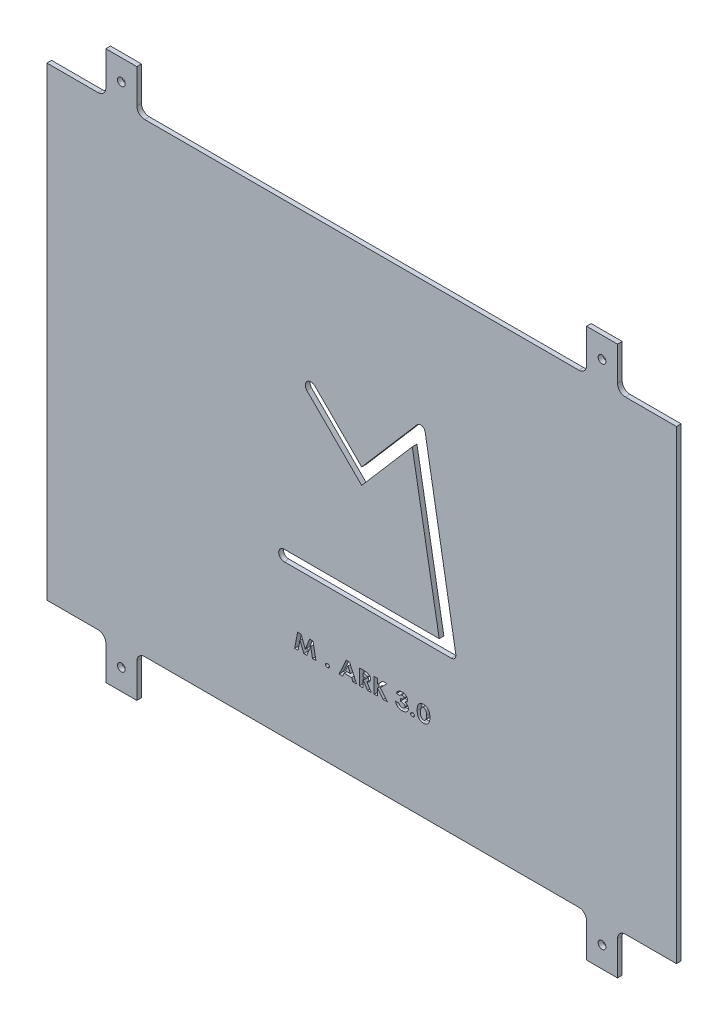
SolidWorks part; units mm, degrees
ref_plane "Front Plane" through (0, 0, 0) normal (0, 0, 1) x (1, 0, 0)
ref_plane "Top Plane" through (0, 0, 0) normal (0, 1, 0) x (1, 0, 0)
ref_plane "Right Plane" through (0, 0, 0) normal (1, 0, 0) x (0, 0, -1)
sketch "Sketch1" plane through (0, 0, 0) normal (0, 0, 1) x (1, 0, 0)
  line L1 (-203, -150) -> (203, -150)
  line L2 (-203, -150) -> (-203, 150)
  line L3 (-203, 150) -> (203, 150)
  line L4 (203, -150) -> (203, 150)
  line L5 (-203, -150) -> (203, 150) construction
  line L6 (-203, 150) -> (203, -150) construction
  point P0 (0, 0)
  dimension "D1" = 406
  dimension "D2" = 300
extrude "Boss-Extrude1" add sketch "Sketch1" along normal blind 3
sketch "Sketch3" plane through (0, 0, 3) normal (0, 0, 1) x (1, 0, 0)
  line L0 (0, -1108.5917) -> (0, 48891.4083) construction
  line L1 (-1206.6722, 0) -> (48793.3278, 0) construction
  line L2 (-50, -45) -> (50, -45)
  line L3 (50, -45) -> (32.6352, 53.4808)
  line L4 (32.6352, 53.4808) -> (0, 15.6001)
  line L5 (0, 15.6001) -> (-35.3553, 50.9554)
  line L6 (-50, -52) -> (57.767, -52)
  line L7 (60.7232, -48.4889) -> (40.9464, 65.8928)
  line L8 (35.7174, 67.3398) -> (0, 25.8815)
  line L9 (0, 25.8815) -> (-30.0237, 55.9052)
  line L10 (-203, -150) -> (203, -150) construction
  line L12 (203, -150) -> (203, 150) construction
  arc A0 (-50, -45) -> (-50, -52) centre (-50, -48.5) ccw
  arc A1 (-35.3553, 50.9554) -> (-30.0237, 55.9052) centre (-32.6895, 53.4303) cw
  arc A2 (60.7232, -48.4889) -> (57.767, -52) centre (57.767, -49) cw
  arc A3 (40.9464, 65.8928) -> (35.7174, 67.3398) centre (37.9902, 65.3817) ccw
  point P7 (0, -45)
  dimension "D7" = 3
  dimension "D8" = 3
  dimension "D14" = 3.5
  dimension "D15" = 3.6375
  dimension "D1" = 80
  dimension "D2" = 100
  dimension "D3" = 100
  dimension "D4" = 45
  dimension "D5" = 50
  dimension "D6" = 45
  dimension "D9" = 98
  dimension "D10" = 145.233
  dimension "D11" = 48.5
  dimension "D12" = 6.7107
  dimension "D13" = 179.81
  dimension "D16" = 42.4599
  dimension "D17" = 32.6895
extrude "Cut-Extrude2" cut sketch "Sketch3" against normal through all
sketch "Sketch4" plane through (0, 0, 3) normal (0, 0, 1) x (1, 0, 0)
  line L0 (0, -1000) -> (0, 49000) construction
  line L1 (-53.8835, -97) -> (53.8835, -97) construction
  line L2 (-50, -52) -> (57.767, -52) construction
  text T0 "<b>M . ARK 3.0</b>" font "Century Gothic" height 10
  point P6 (0, -97)
  dimension "D1" = 45
extrude "Cut-Extrude3" cut sketch "Sketch4" against normal through all
sketch "Sketch5" plane through (0, 0, 3) normal (0, 0, 1) x (1, 0, 0)
  line L0 (0, -1000) -> (0, 49000) construction
  line L1 (-155, -891.8675) -> (-155, 49108.1325) construction
  line L2 (-203, 150) -> (-203, -150) construction
  line L3 (203, 150) -> (-203, 150) construction
  line L4 (-165, 150) -> (-145, 150)
  line L5 (-165, 150) -> (-165, 177)
  line L6 (-165, 177) -> (-145, 177)
  line L7 (-145, 150) -> (-145, 177)
  line L8 (145, 150) -> (145, 177)
  line L9 (165, 177) -> (145, 177)
  line L10 (165, 150) -> (165, 177)
  line L11 (165, 150) -> (145, 150)
  line L12 (-1200, 0) -> (48800, 0) construction
  line L13 (165, -150) -> (145, -150)
  line L14 (165, -150) -> (165, -177)
  line L15 (165, -177) -> (145, -177)
  line L16 (145, -150) -> (145, -177)
  line L17 (-145, -150) -> (-145, -177)
  line L18 (-165, -177) -> (-145, -177)
  line L19 (-165, -150) -> (-165, -177)
  line L20 (-165, -150) -> (-145, -150)
  circle A0 centre (-155, 163.5) radius 2.5
  circle A1 centre (155, 163.5) radius 2.5
  circle A2 centre (155, -163.5) radius 2.5
  circle A3 centre (-155, -163.5) radius 2.5
  point P13 (-155, 177)
  point P16 (-165, 163.5)
  point P26 (-203, 0)
  dimension "D4" = 5
  dimension "D1" = 48
  dimension "D2" = 27
  dimension "D3" = 20
extrude "Boss-Extrude3" add sketch "Sketch5" against normal blind 3 contours L11 L10 L9 L8 A1 | L13 L16 L15 L14 A2 | L20 L19 L18 L17 A3 | L4 L7 L6 L5 A0 region at (-164.664, 163.5, 3) region at (145.336, 163.5, 3) region at (164.664, -163.5, 3) region at (-145.336, -163.5, 3)
fillet "Fillet1" radius 5 8 edges at (-165, -150, 1.5) (-145, -150, 1.5) (145, -150, 1.5) (165, -150, 1.5) (-145, 150, 1.5) (-165, 150, 1.5) (145, 150, 1.5) (165, 150, 1.5)
